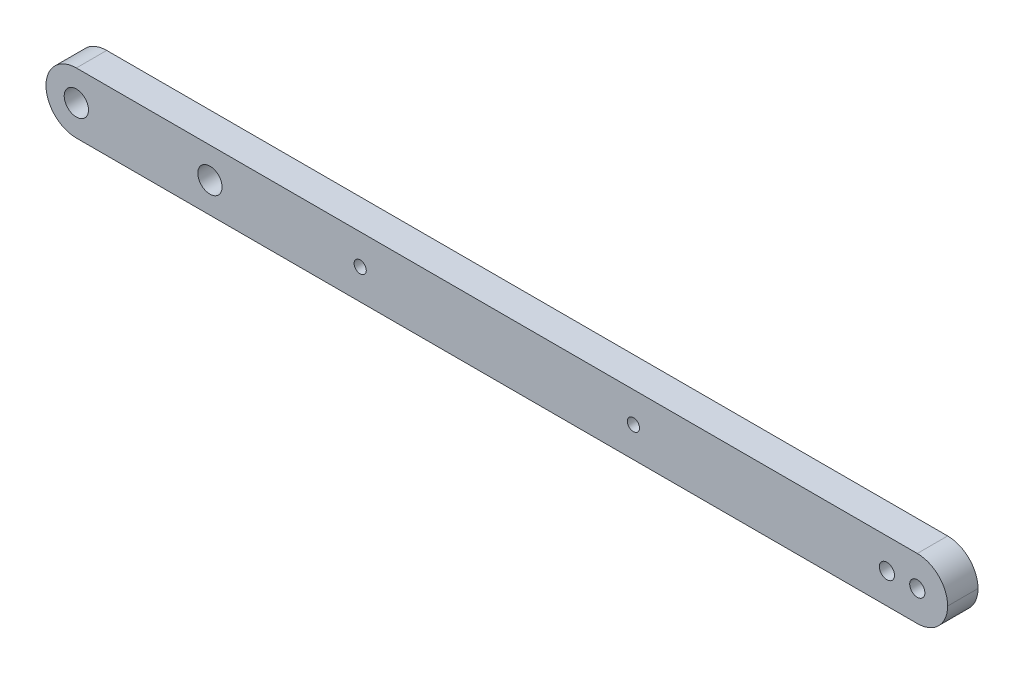
SolidWorks part; units mm, degrees
material "AISI 316 Barre d'acier inoxydable recuit (SS)"
ref_plane "Plan de face" through (0, 0, 0) normal (0, 0, 1) x (1, 0, 0)
ref_plane "Plan de dessus" through (0, 0, 0) normal (0, 1, 0) x (1, 0, 0)
ref_plane "Plan de droite" through (0, 0, 0) normal (1, 0, 0) x (0, 0, -1)
sketch "Esquisse1" plane through (0, 0, 0) normal (0, 0, 1) x (1, 0, 0)
  line L0 (0, 10) -> (297, 10) construction
  line L1 (0, 20) -> (297, 20)
  line L2 (0, 20) -> (0, 0)
  line L3 (0, 0) -> (297, 0)
  line L4 (297, 20) -> (297, 0)
  line L5 (148.5, 20) -> (148.5, 0) construction
  circle A0 centre (10, 10) radius 4
  circle A1 centre (54, 10) radius 4
  circle A2 centre (277, 10) radius 2.5
  circle A3 centre (287, 10) radius 2.5
  circle A4 centre (103.5, 10) radius 2
  circle A5 centre (193.5, 10) radius 2
  dimension "D3" = 8
  dimension "D4" = 44
  dimension "D7" = 5
  dimension "D9" = 90
  dimension "D10" = 4
  dimension "D11" = 90
  dimension "D1" = 20
  dimension "D2" = 297
  dimension "D5" = 10
  dimension "D6" = 10
  dimension "D8" = 10
extrude "Boss.-Extru.1" add sketch "Esquisse1" along normal blind 10
fillet "Congé1" radius 10 4 edges at (0, 0, 5) (0, 20, 5) (297, 0, 5) (297, 20, 5)
